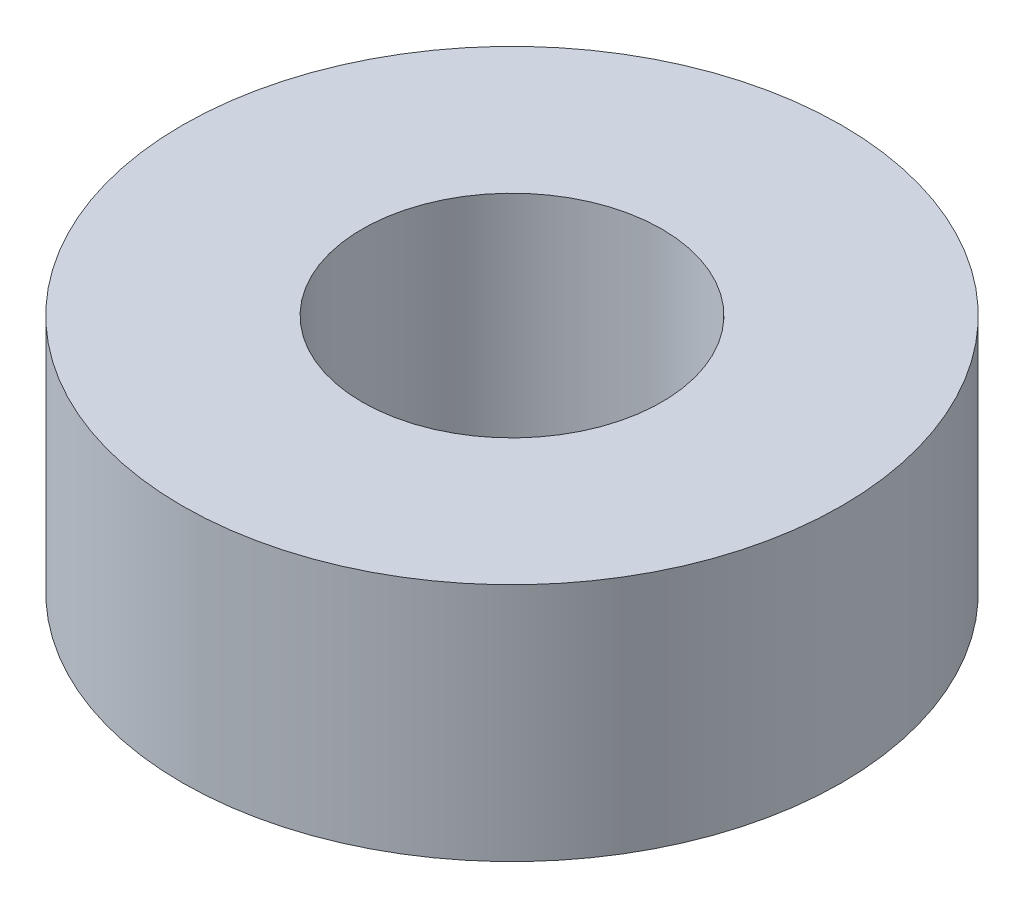
SolidWorks part; units mm, degrees
ref_plane "Front Plane" through (0, 0, 0) normal (0, 0, 1) x (1, 0, 0)
ref_plane "Top Plane" through (0, 0, 0) normal (0, 1, 0) x (1, 0, 0)
ref_plane "Right Plane" through (0, 0, 0) normal (1, 0, 0) x (0, 0, -1)
sketch "Sketch1" plane through (0, 0, 0) normal (0, 1, 0) x (1, 0, 0)
  circle A0 centre (0, 0) radius 2.5
  circle A1 centre (0, 0) radius 5.5
  dimension "D1" = 5
  dimension "D2" = 11
extrude "Boss-Extrude1" add sketch "Sketch1" along normal blind 2 and the other way blind 2
